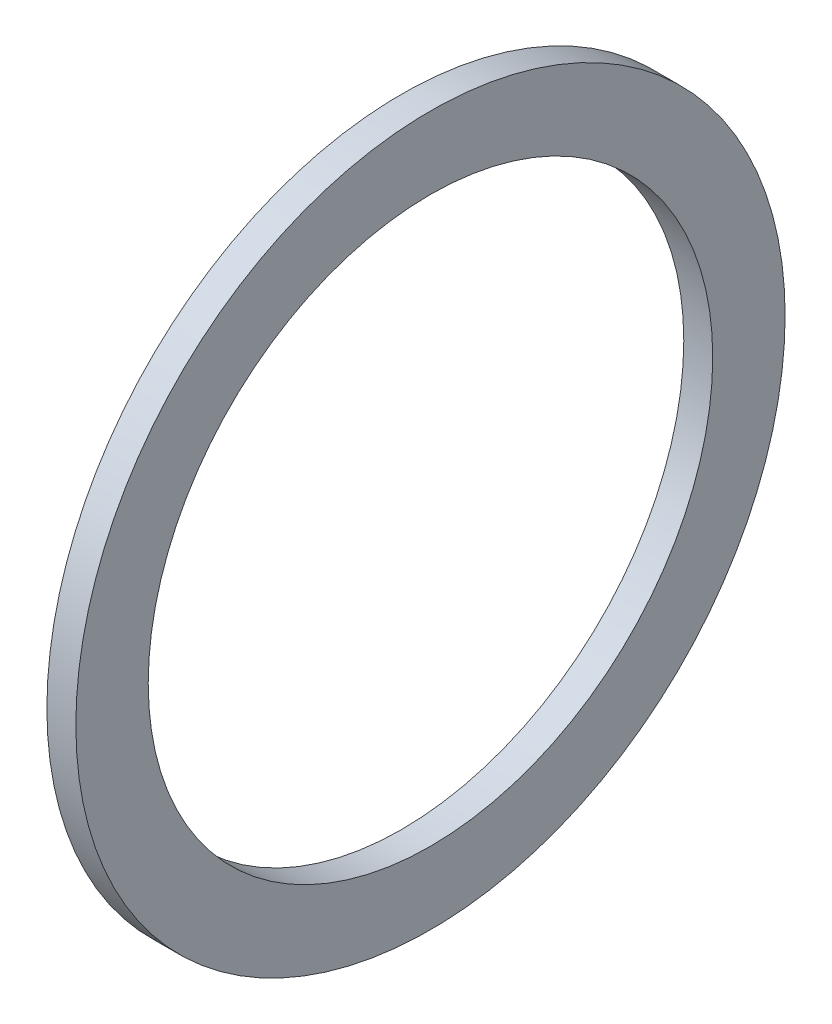
SolidWorks part; units mm, degrees
ref_plane "Спереди" through (0, 0, 0) normal (0, 0, 1) x (1, 0, 0)
ref_plane "Сверху" through (0, 0, 0) normal (0, 1, 0) x (1, 0, 0)
ref_plane "Справа" through (0, 0, 0) normal (1, 0, 0) x (0, 0, -1)
sketch "Эскиз1" plane through (0, 0, 0) normal (1, 0, 0) x (0, 0, -1)
  circle A0 centre (0, 0) radius 24.5
  circle A1 centre (0, 0) radius 19.5
  dimension "D1" = 49
  dimension "D2" = 39
extrude "Бобышка-Вытянуть1" add sketch "Эскиз1" along normal blind 2
